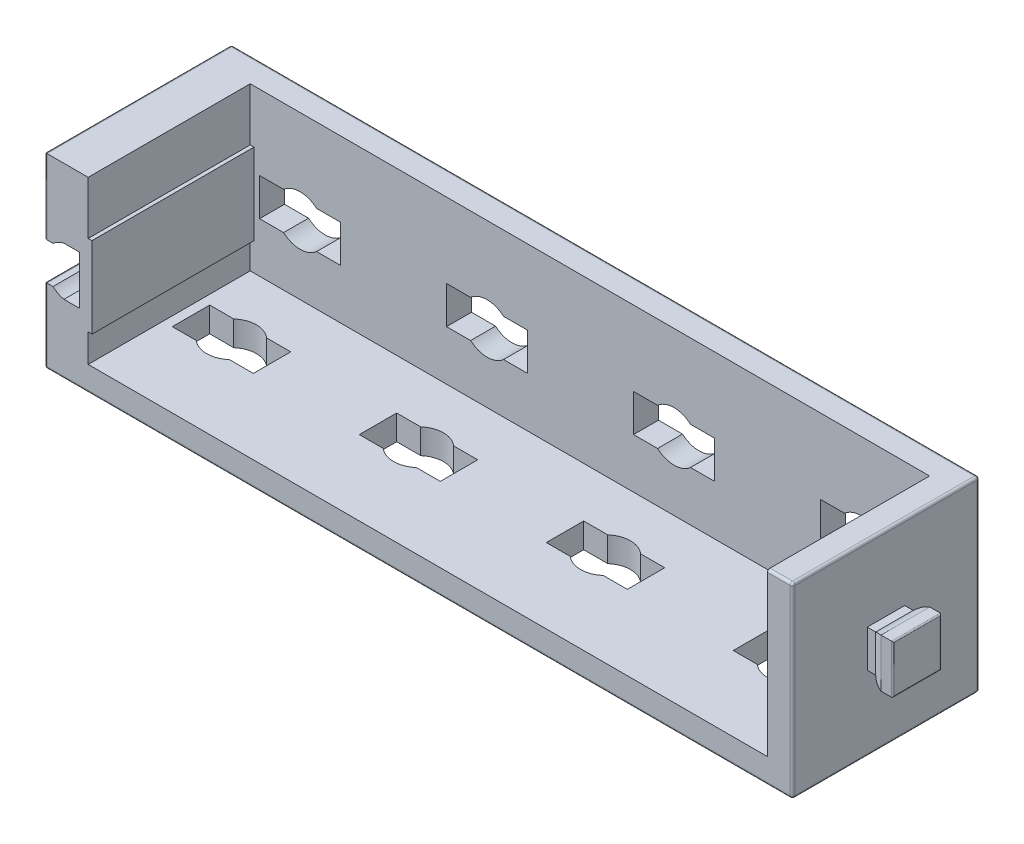
SolidWorks part; units mm, degrees
ref_plane "前视基准面" through (0, 0, 0) normal (0, 0, 1) x (1, 0, 0)
ref_plane "上视基准面" through (0, 0, 0) normal (0, 1, 0) x (1, 0, 0)
ref_plane "右视基准面" through (0, 0, 0) normal (1, 0, 0) x (0, 0, -1)
sketch "草图1" plane through (0, 0, 0) normal (0, 0, 1) x (1, 0, 0)
  line L1 (-30, 0) -> (30, 0)
  line L2 (-30, 0) -> (-30, 15)
  line L3 (-30, 15) -> (30, 15)
  line L4 (30, 0) -> (30, 15)
extrude "凸台-拉伸1" add sketch "草图1" along normal blind 7.5 and the other way blind 7.5
sketch "草图2" plane through (30, 0, 0) normal (1, 0, 0) x (0, 0, -1)
  line L1 (-1.5, 6) -> (1.5, 6)
  line L2 (-1.5, 6) -> (-1.5, 9)
  line L3 (-1.5, 9) -> (1.5, 9)
  line L4 (1.5, 6) -> (1.5, 9)
extrude "凸台-拉伸2" add sketch "草图2" along normal blind 1
sketch "草图3" plane through (0, 0, 1.5) normal (0, 0, 1) x (1, 0, 0)
  line L0 (32.5, 9.45) -> (32.5, 5.55)
  line L1 (32.5, 9.45) -> (31.5556, 9.45)
  line L2 (32.5, 5.55) -> (31.5556, 5.55)
  line L5 (30.6771, 9) -> (30.6771, 6)
  arc A0 (30.6771, 6) -> (31.5556, 5.55) centre (32, 7.5) ccw
  arc A1 (31.5556, 9.45) -> (30.6771, 9) centre (32, 7.5) ccw
extrude "凸台-拉伸3" add sketch "草图3" along normal blind 1 and the other way blind 4
sketch "草图4" plane through (0, 9.45, 0) normal (0, 1, 0) x (-1, 0, 0)
  line L0 (-32.5, -1.95) -> (-31.5556, -1.95)
  line L1 (-30.6771, -2.5) -> (-32.5, -2.5)
  line L2 (-30.6771, -2.5) -> (-30.6771, -1.5)
  line L3 (-30.6771, 2.5) -> (-32.5, 2.5)
  line L4 (-32.5, -2.5) -> (-32.5, -1.95)
  line L5 (-32.5, 1.95) -> (-31.5556, 1.95)
  line L6 (-30.6771, 1.5) -> (-30.6771, 2.5)
  line L7 (-32.5, 1.95) -> (-32.5, 2.5)
  arc A1 (-31.5556, -1.95) -> (-30.6771, -1.5) centre (-32, 0) ccw
  arc A2 (-30.6771, 1.5) -> (-31.5556, 1.95) centre (-32, 0) ccw
extrude "切除-拉伸1" cut sketch "草图4" against normal up to next
sketch "草图5" plane through (0, 0, 7.5) normal (0, 0, 1) x (1, 0, 0)
  line L0 (30, 15) -> (-30, 15) construction
  line L1 (-26.5, 2) -> (28, 2)
  line L2 (-26.5, 2) -> (-26.5, 15)
  line L3 (-26.5, 15) -> (28, 15)
  line L4 (28, 2) -> (28, 15)
extrude "切除-拉伸2" cut sketch "草图5" against normal blind 13
sketch "草图6" plane through (0, 0, 7.5) normal (0, 0, 1) x (1, 0, 0)
  line L0 (-27.2, 9.45) -> (-27.2, 5.55)
  line L1 (-30, 15) -> (-30, 0) construction
  line L2 (-30, 9) -> (-29.3229, 9)
  line L3 (-30, 9) -> (-30, 6)
  line L4 (-30, 6) -> (-29.3229, 6)
  line L5 (-27.2, 9.45) -> (-28.4444, 9.45)
  line L6 (-27.2, 5.55) -> (-28.4444, 5.55)
  arc A0 (-29.3229, 6) -> (-28.4444, 5.55) centre (-28, 7.5) ccw
  arc A1 (-28.4444, 9.45) -> (-29.3229, 9) centre (-28, 7.5) ccw
extrude "切除-拉伸3" cut sketch "草图6" against normal blind 9.45
sketch "草图7" plane through (0, 0, 7.5) normal (0, 0, 1) x (1, 0, 0)
  line L0 (-26.5, 15) -> (-26.5, 2) construction
  line L1 (-26.5, 10.75) -> (-26.2, 10.75)
  line L2 (-26.5, 10.75) -> (-26.5, 4.25)
  line L3 (-26.5, 4.25) -> (-26.2, 4.25)
  line L4 (-26.2, 10.75) -> (-26.2, 4.25)
extrude "凸台-拉伸4" add sketch "草图7" against normal up to next
sketch "草图8" plane through (0, 0, -5.5) normal (0, 0, 1) x (1, 0, 0)
  line L0 (-21.1771, 9) -> (-19.25, 9)
  line L1 (-25.75, 9) -> (-23.8229, 9)
  line L2 (-25.75, 9) -> (-25.75, 6)
  line L3 (-25.75, 6) -> (-23.8229, 6)
  line L4 (-19.25, 9) -> (-19.25, 6)
  line L5 (-10.75, 9) -> (-8.8229, 9)
  line L6 (-10.75, 9) -> (-10.75, 6)
  line L7 (-10.75, 6) -> (-8.8229, 6)
  line L8 (-4.25, 9) -> (-4.25, 6)
  line L9 (-21.1771, 6) -> (-19.25, 6)
  line L10 (-6.1771, 9) -> (-4.25, 9)
  line L11 (-6.1771, 6) -> (-4.25, 6)
  line L12 (0, -1.8609) -> (0, 16.3844) construction
  line L13 (6.1771, 6) -> (4.25, 6)
  line L14 (6.1771, 9) -> (4.25, 9)
  line L15 (21.1771, 6) -> (19.25, 6)
  line L16 (4.25, 9) -> (4.25, 6)
  line L17 (10.75, 6) -> (8.8229, 6)
  line L18 (10.75, 9) -> (10.75, 6)
  line L19 (10.75, 9) -> (8.8229, 9)
  line L20 (19.25, 9) -> (19.25, 6)
  line L21 (25.75, 6) -> (23.8229, 6)
  line L22 (25.75, 9) -> (25.75, 6)
  line L23 (25.75, 9) -> (23.8229, 9)
  line L24 (21.1771, 9) -> (19.25, 9)
  arc A0 (-23.8229, 6) -> (-21.1771, 6) centre (-22.5, 7.5) ccw
  arc A1 (-8.8229, 6) -> (-6.1771, 6) centre (-7.5, 7.5) ccw
  arc A2 (-21.1771, 9) -> (-23.8229, 9) centre (-22.5, 7.5) ccw
  arc A3 (-6.1771, 9) -> (-8.8229, 9) centre (-7.5, 7.5) ccw
  arc A4 (6.1771, 9) -> (8.8229, 9) centre (7.5, 7.5) cw
  arc A5 (21.1771, 9) -> (23.8229, 9) centre (22.5, 7.5) cw
  arc A6 (8.8229, 6) -> (6.1771, 6) centre (7.5, 7.5) cw
  arc A7 (23.8229, 6) -> (21.1771, 6) centre (22.5, 7.5) cw
extrude "切除-拉伸4" cut sketch "草图8" against normal up to next
sketch "草图9" plane through (0, 2, 0) normal (0, 1, 0) x (-1, 0, 0)
  line L0 (21.1771, -1.5) -> (19.25, -1.5)
  line L1 (10.75, -1.5) -> (8.8229, -1.5)
  line L2 (10.75, -1.5) -> (10.75, 1.5)
  line L3 (10.75, 1.5) -> (8.8229, 1.5)
  line L4 (4.25, -1.5) -> (4.25, 1.5)
  line L5 (25.75, -1.5) -> (23.8229, -1.5)
  line L6 (25.75, -1.5) -> (25.75, 1.5)
  line L7 (25.75, 1.5) -> (23.8229, 1.5)
  line L8 (19.25, -1.5) -> (19.25, 1.5)
  line L9 (21.1771, 1.5) -> (19.25, 1.5)
  line L10 (6.1771, -1.5) -> (4.25, -1.5)
  line L11 (6.1771, 1.5) -> (4.25, 1.5)
  line L12 (0, -8.9404) -> (0, 8.8226) construction
  line L13 (-6.1771, 1.5) -> (-4.25, 1.5)
  line L14 (-6.1771, -1.5) -> (-4.25, -1.5)
  line L15 (-21.1771, 1.5) -> (-19.25, 1.5)
  line L16 (-19.25, -1.5) -> (-19.25, 1.5)
  line L17 (-25.75, 1.5) -> (-23.8229, 1.5)
  line L18 (-25.75, -1.5) -> (-25.75, 1.5)
  line L19 (-25.75, -1.5) -> (-23.8229, -1.5)
  line L20 (-4.25, -1.5) -> (-4.25, 1.5)
  line L21 (-10.75, 1.5) -> (-8.8229, 1.5)
  line L22 (-10.75, -1.5) -> (-10.75, 1.5)
  line L23 (-10.75, -1.5) -> (-8.8229, -1.5)
  line L24 (-21.1771, -1.5) -> (-19.25, -1.5)
  arc A0 (8.8229, 1.5) -> (6.1771, 1.5) centre (7.5, 0) ccw
  arc A1 (23.8229, 1.5) -> (21.1771, 1.5) centre (22.5, 0) ccw
  arc A2 (21.1771, -1.5) -> (23.8229, -1.5) centre (22.5, 0) ccw
  arc A3 (6.1771, -1.5) -> (8.8229, -1.5) centre (7.5, 0) ccw
  arc A4 (-6.1771, -1.5) -> (-8.8229, -1.5) centre (-7.5, 0) cw
  arc A5 (-21.1771, -1.5) -> (-23.8229, -1.5) centre (-22.5, 0) cw
  arc A6 (-23.8229, 1.5) -> (-21.1771, 1.5) centre (-22.5, 0) cw
  arc A7 (-8.8229, 1.5) -> (-6.1771, 1.5) centre (-7.5, 0) cw
extrude "切除-拉伸5" cut sketch "草图9" against normal up to next
fillet "圆角1" radius 0.1 4 edges at (32.5, 9.45, 0) (32.5, 7.5, -1.95) (32.5, 5.55, 0) (32.5, 7.5, 1.95)
fillet "圆角2" radius 0.2 16 edges at (-30, 3, 7.5) (-30, 0, 0) (-30, 7.5, -7.5) (-30, 15, 0) (-30, 12, 7.5) (-30, 9, 2.775) (-30, 7.5, -1.95) (-30, 6, 2.775) (0, 0, -7.5) (0, 0, 7.5) (0, 15, -7.5) (30, 0, 0) (30, 7.5, -7.5) (30, 15, 0) (29, 15, 7.5) (30, 7.5, 7.5)
